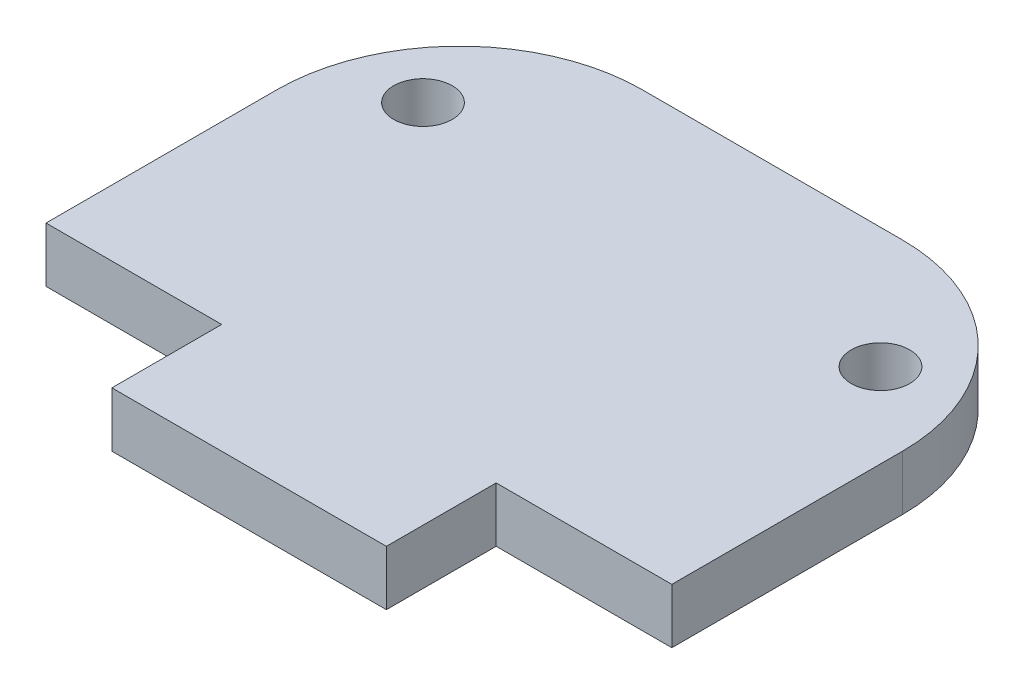
SolidWorks part; units mm, degrees
material "MDF"
ref_plane "Plano frontal" through (0, 0, 0) normal (0, 0, 1) x (1, 0, 0)
ref_plane "Plano superior" through (0, 0, 0) normal (0, 1, 0) x (1, 0, 0)
ref_plane "Plano direito" through (0, 0, 0) normal (1, 0, 0) x (0, 0, -1)
ref_plane "Plano1" through (0, -3, 0) normal (0, -1, 0) x (1, 0, 0)
sketch "Esboço1" plane through (0, -3, 0) normal (0, -1, 0) x (1, 0, 0)
  line L0 (-7.1, -28.6) -> (7.1, -28.6)
  line L1 (17.1, -18.6) -> (17.1, -6)
  line L2 (17.1, -6) -> (7.5, -6)
  line L3 (7.5, -6) -> (7.5, 0)
  line L4 (7.5, 0) -> (-7.5, 0)
  line L5 (-7.5, 0) -> (-7.5, -6)
  line L6 (-7.5, -6) -> (-17.1, -6)
  line L7 (-17.1, -6) -> (-17.1, -18.6)
  line L8 (-12.5, -22) -> (12.5, -22) construction
  line L9 (-7.5, -6) -> (7.5, -6) construction
  arc A0 (7.1, -28.6) -> (17.1, -18.6) centre (7.1, -18.6) ccw
  arc A1 (-17.1, -18.6) -> (-7.1, -28.6) centre (-7.1, -18.6) ccw
  circle A2 centre (-12.5, -22) radius 1.6
  circle A3 centre (12.5, -22) radius 1.6
  point P16 (0, 0)
  point P17 (0, -22)
  point P18 (0, -6)
  dimension "D1" = 25
  dimension "D2" = 3.2
  dimension "D6" = 10
  dimension "D3" = 15
  dimension "D4" = 6
  dimension "D5" = 22.6
  dimension "D7" = 6.6
  dimension "D8" = 4.6
extrude "Ressalto-extrusão1" add sketch "Esboço1" against normal blind 3
